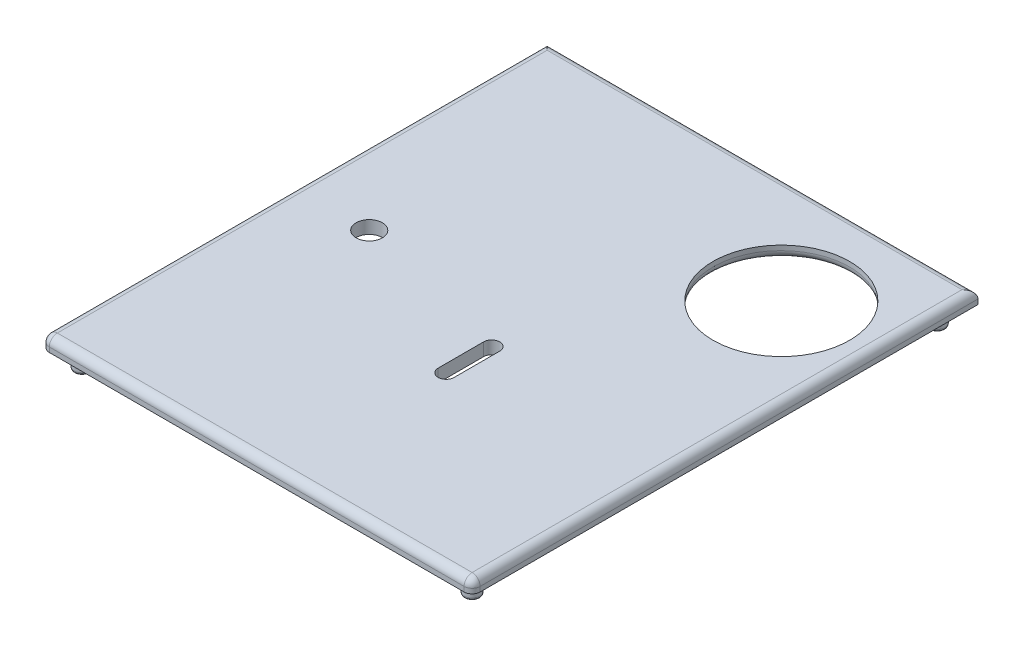
SolidWorks part; units mm, degrees
ref_plane "Front Plane" through (0, 0, 0) normal (0, 0, 1) x (1, 0, 0)
ref_plane "Top Plane" through (0, 0, 0) normal (0, 1, 0) x (1, 0, 0)
ref_plane "Right Plane" through (0, 0, 0) normal (1, 0, 0) x (0, 0, -1)
sketch "Sketch1" plane through (0, 0, 0) normal (0, 1, 0) x (1, 0, 0)
  line L0 (0, 65.5188) -> (0, -104.2885) construction
  line L1 (-40.2, -47.2) -> (40.2, -47.2)
  line L2 (-40.2, -47.2) -> (-40.2, 47.2)
  line L3 (-40.2, 47.2) -> (40.2, 47.2)
  line L4 (40.2, -47.2) -> (40.2, 47.2)
  line L5 (-40.2, -47.2) -> (40.2, 47.2) construction
  line L6 (-40.2, 47.2) -> (40.2, -47.2) construction
  line L7 (-85.033, 0) -> (102.3958, 0) construction
  circle A0 centre (-36.4, 43.4) radius 1.6 construction
  circle A1 centre (36.4, 43.4) radius 1.6 construction
  circle A2 centre (36.4, -43.4) radius 1.6 construction
  circle A3 centre (-36.4, -43.4) radius 1.6 construction
  circle A4 centre (-36.4, 43.4) radius 1.45
  circle A5 centre (36.4, 43.4) radius 1.45
  circle A6 centre (36.4, -43.4) radius 1.45
  circle A7 centre (-36.4, -43.4) radius 1.45
  circle A8 centre (23.65, 27.05) radius 12.75
  circle A9 centre (-26.2, 0) radius 2.45
  point P0 (0, 0)
  dimension "D3" = 3.2
  dimension "D6" = 2.9
  dimension "D7" = 2.9
  dimension "D8" = 2.9
  dimension "D9" = 2.9
  dimension "D10" = 4.9
  dimension "D12" = 25.5
  dimension "D1" = 94.4
  dimension "D2" = 80.4
  dimension "D4" = 3.8
  dimension "D5" = 3.8
  dimension "D11" = 14
  dimension "D13" = 16.55
  dimension "D14" = 20.15
extrude "Boss-Extrude1" add sketch "Sketch1" along normal blind 2.4 contours A7 | L1 L4 L3 L2 A9 A8 A7 A6 A5 A4 | A4 | A5 | A6 region at (-1.6469, 0, 1.964) region at (-36.4, 0, -43.4) region at (36.4, 0, -43.4) region at (36.4, 0, 43.4) region at (-36.4, 0, 43.4)
fillet "Fillet1" radius 1.5 7 edges at (40.2, 1.2, 47.2) (23.65, 0, -14.3) (40.2, 2.4, 0) (0, 2.4, -47.2) (-40.2, 1.2, 47.2) (-40.2, 2.4, 0) (0, 2.4, 47.2)
sketch "Sketch2" plane through (0, 0, 0) normal (0, -1, 0) x (1, 0, 0)
  line L0 (40.2, 45.7) -> (40.2, -47.2) construction
  line L1 (35.9, 4.2) -> (37.9, 4.2)
  line L2 (35.9, 4.2) -> (35.9, -7.8)
  line L3 (35.9, -7.8) -> (37.9, -7.8)
  line L4 (37.9, 4.2) -> (37.9, -7.8)
  line L5 (35.9, 4.2) -> (37.9, -7.8) construction
  line L6 (35.9, -7.8) -> (37.9, 4.2) construction
  line L8 (-38.7, 47.2) -> (38.7, 47.2) construction
  line L9 (0, 58.3679) -> (0, -60.832) construction
  line L10 (-35.9, -7.8) -> (-37.9, -7.8)
  line L11 (-37.9, 4.2) -> (-37.9, -7.8)
  line L12 (-35.9, 4.2) -> (-37.9, 4.2)
  line L13 (-35.9, 4.2) -> (-35.9, -7.8)
  point P0 (36.9, -1.8)
  point P16 (-36.9, -1.8)
  dimension "D1" = 2.3
  dimension "D2" = 2
  dimension "D3" = 12
  dimension "D4" = 43
extrude "Boss-Extrude2" add sketch "Sketch2" along normal blind 2.6
fillet "Fillet2" radius 0.5 2 edges at (37.9, -2.6, -1.8) (-37.9, -2.6, -1.8)
extrude "Boss-Extrude3" add sketch "Sketch1<4>" against normal blind 3.5 from surface contours A5 | A4 | A7 | A6 region at (-36.4, 0, -43.4) region at (36.4, 0, -43.4) region at (36.4, 0, 43.4) region at (-36.4, 0, 43.4) starting at face at (36.9, 0, -1.8)
sketch "Sketch1<4>" plane through (0, 0, 0) normal (0, 1, 0) x (1, 0, 0) same geometry as "Sketch1"
fillet "Fillet3" radius 0.5 4 edges at (36.4, -3.5, -41.95) (-36.4, -3.5, -41.95) (-36.4, -3.5, 44.85) (36.4, -3.5, 44.85)
sketch "Sketch3" plane through (0, 2.4, 0) normal (0, 1, 0) x (1, 0, 0)
  line L0 (4, -7.35) -> (4, -15.85) construction
  line L1 (5.5, -7.35) -> (5.5, -15.85)
  line L2 (2.5, -7.35) -> (2.5, -15.85)
  line L3 (40.2, 47.2) -> (40.2, -45.7) construction
  line L4 (38.7, -47.2) -> (-38.7, -47.2) construction
  arc A0 (5.5, -7.35) -> (2.5, -7.35) centre (4, -7.35) ccw
  arc A1 (2.5, -15.85) -> (5.5, -15.85) centre (4, -15.85) ccw
  point P2 (4, -11.6)
  point P11 (4, -5.85)
  dimension "D4" = 10
  dimension "D1" = 36.2
  dimension "D2" = 35.6
  dimension "D3" = 3
extrude "Cut-Extrude1" cut sketch "Sketch3" against normal through all both and the other way through all
